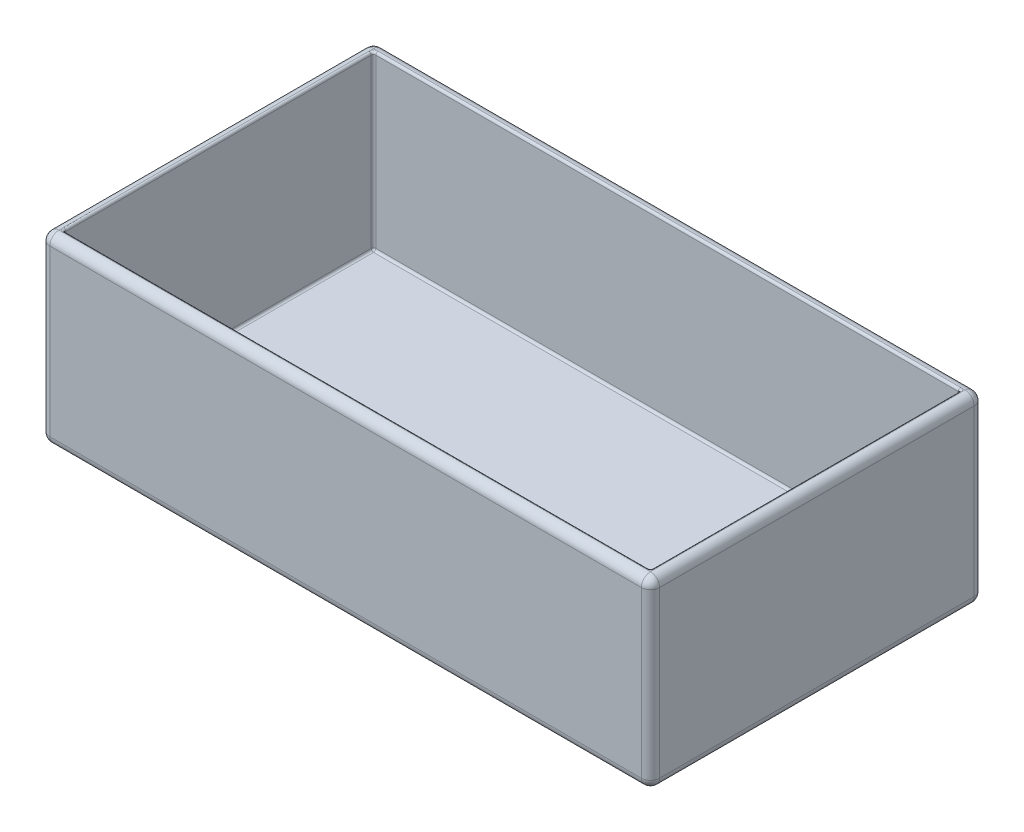
SolidWorks part; units mm, degrees
material "Galvanized Steel"
ref_plane "Front Plane" through (0, 0, 0) normal (0, 0, 1) x (1, 0, 0)
ref_plane "Top Plane" through (0, 0, 0) normal (0, 1, 0) x (1, 0, 0)
ref_plane "Right Plane" through (0, 0, 0) normal (1, 0, 0) x (0, 0, -1)
sketch "Sketch1" plane through (0, 0, 0) normal (0, 1, 0) x (1, 0, 0)
  line L1 (-168.91, 92.202) -> (168.91, 92.202)
  line L2 (-168.91, 92.202) -> (-168.91, -92.202)
  line L3 (-168.91, -92.202) -> (168.91, -92.202)
  line L4 (168.91, 92.202) -> (168.91, -92.202)
  line L5 (-168.91, 92.202) -> (168.91, -92.202) construction
  line L6 (-168.91, -92.202) -> (168.91, 92.202) construction
  point P0 (0, 0)
  dimension "D1" = 337.82
  dimension "D2" = 184.404
extrude "Boss-Extrude1" add sketch "Sketch1" along normal blind 101.6
shell "Shell1" thickness 6.35 removed face at (0, 101.6, 0)
fillet "Fillet1" radius 5.08 12 edges at (0, 101.6, -92.202) (0, 0, -92.202) (168.91, 101.6, 0) (168.91, 50.8, -92.202) (168.91, 0, 0) (0, 101.6, 92.202) (168.91, 50.8, 92.202) (0, 0, 92.202) (-168.91, 50.8, -92.202) (-168.91, 101.6, 0) (-168.91, 50.8, 92.202) (-168.91, 0, 0)
fillet "Fillet2" radius 1.27 12 edges at (0, 101.6, 85.852) (162.56, 101.6, 0) (162.56, 53.975, 85.852) (0, 101.6, -85.852) (162.56, 53.975, -85.852) (0, 6.35, 85.852) (0, 6.35, -85.852) (162.56, 6.35, 0) (-162.56, 53.975, 85.852) (-162.56, 101.6, 0) (-162.56, 53.975, -85.852) (-162.56, 6.35, 0)
